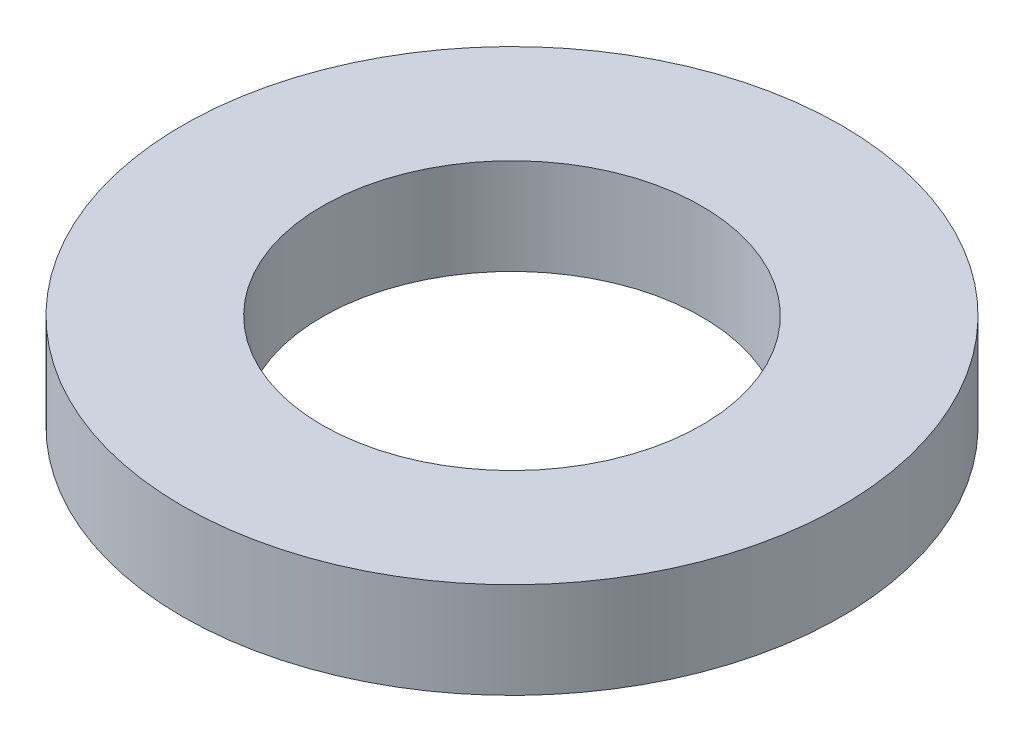
SolidWorks part; units mm, degrees
ref_plane "Front Plane" through (0, 0, 0) normal (0, 0, 1) x (1, 0, 0)
ref_plane "Top Plane" through (0, 0, 0) normal (0, 1, 0) x (1, 0, 0)
ref_plane "Right Plane" through (0, 0, 0) normal (1, 0, 0) x (0, 0, -1)
sketch "Sketch1" plane through (0, 0, 0) normal (0, 1, 0) x (1, 0, 0)
  circle A0 centre (0, 0) radius 82.5
  dimension "FLANGE_OD" = 165
extrude "Boss-Extrude1" add sketch "Sketch1" along normal blind 24
sketch "Sketch2" plane through (0, 0, 0) normal (0, 1, 0) x (1, 0, 0)
  circle A0 centre (0, 0) radius 47.5
  dimension "BORE_D" = 95
extrude "Cut-Extrude1" cut sketch "Sketch2" along normal through all
sketch "Sketch3" plane through (0, 24, 0) normal (0, 1, 0) x (1, 0, 0)
  circle A0 centre (0, 0) radius 27.6866 construction
  circle A1 centre (-27.6866, 0) radius 6.2017
  dimension "BOLT_D" = 12.4034
  dimension "BOLT_PCD" = 55.3732
extrude "Cut-Extrude2" cut sketch "Sketch3" against normal blind 17.9693 rebuild error yes
pattern_circular "CirPattern1" count 3 over 360 rebuild error yes
